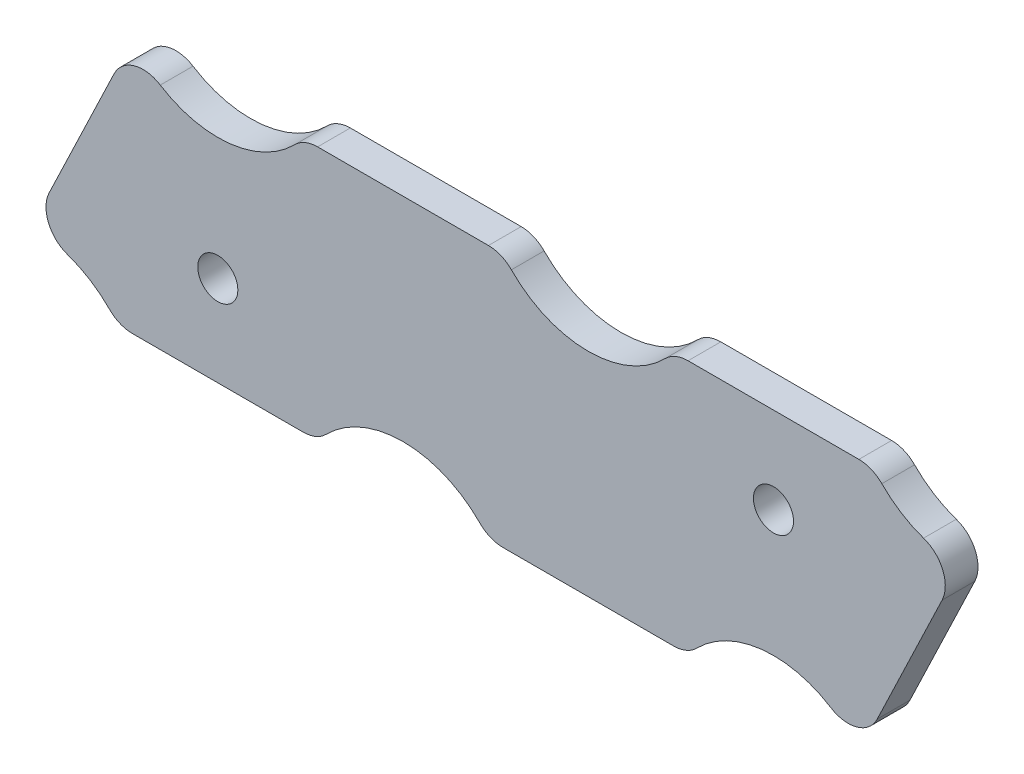
SolidWorks part; units mm, degrees
material "3003-H14"
ref_plane "X-Y Datum" through (0, 0, 0) normal (0, 0, 1) x (1, 0, 0)
ref_plane "X-Z Datum" through (0, 0, 0) normal (0, 1, 0) x (1, 0, 0)
ref_plane "Y-Z Datum" through (0, 0, 0) normal (1, 0, 0) x (0, 0, -1)
sketch "Sketch3" plane through (0, 0, 0) normal (0, 0, 1) x (1, 0, 0)
  line L0 (10.775, 10.775) -> (22.275, 34.775) construction
  line L1 (0, 0) -> (156.4633, 0) construction
  line L2 (0, 0) -> (0, 56.3098) construction
  line L3 (0, 56.3098) -> (156.4633, 56.3098) construction
  line L4 (156.4633, 0) -> (156.4633, 56.3098) construction
  line L5 (33.775, 10.775) -> (45.275, 34.775) construction
  line L6 (56.775, 10.775) -> (68.275, 34.775) construction
  line L7 (16.525, 22.775) -> (62.525, 22.775) construction
  line L8 (33.775, 10.775) -> (22.275, 34.775) construction
  line L9 (45.275, 34.775) -> (56.775, 10.775) construction
  line L10 (10.775, 10.775) -> (33.775, 10.775) construction
  line L11 (56.775, 10.775) -> (33.775, 10.775) construction
  line L12 (22.275, 34.775) -> (45.275, 34.775) construction
  line L13 (68.275, 34.775) -> (45.275, 34.775) construction
  line L14 (22.275, 34.775) -> (22.275, 10.775) construction
  line L15 (45.275, 10.775) -> (45.275, 34.775) construction
  line L16 (33.775, 10.775) -> (33.775, 34.775) construction
  line L17 (56.775, 34.775) -> (56.775, 10.775) construction
  line L18 (13.4804, 9.4786) -> (24.9804, 33.4786)
  line L19 (36.4804, 9.4786) -> (47.9804, 33.4786)
  line L20 (59.4804, 9.4786) -> (70.9804, 33.4786)
  line L21 (8.0696, 12.0714) -> (19.5696, 36.0714)
  line L22 (31.0696, 12.0714) -> (42.5696, 36.0714)
  line L23 (54.0696, 12.0714) -> (65.5696, 36.0714)
  line L24 (17.8152, 18.525) -> (57.1619, 18.525)
  line L25 (21.8881, 27.025) -> (61.2348, 27.025)
  line L26 (16.525, 27.025) -> (62.525, 27.025) construction
  line L27 (16.525, 18.525) -> (62.525, 18.525) construction
  line L28 (16.0692, 14.8813) -> (28.4808, 14.8813)
  line L29 (39.9808, 30.6687) -> (27.5692, 30.6687)
  line L48 (56.775, 10.775) -> (68.275, 10.775) construction
  line L49 (68.275, 10.775) -> (68.275, 34.775) construction
  line L50 (62.9808, 30.6687) -> (50.5692, 30.6687)
  line L51 (39.0692, 14.8813) -> (51.4808, 14.8813)
  circle A0 centre (10.775, 10.775) radius 10.775 construction
  circle A1 centre (33.775, 10.775) radius 10.775 construction
  circle A2 centre (22.275, 34.775) radius 10.775 construction
  circle A3 centre (45.275, 34.775) radius 10.775 construction
  circle A4 centre (68.275, 34.775) radius 10.775 construction
  circle A5 centre (56.775, 10.775) radius 10.775 construction
  circle A6 centre (10.775, 10.775) radius 4.7 construction
  circle A7 centre (33.775, 10.775) radius 4.7 construction
  circle A8 centre (56.775, 10.775) radius 4.7 construction
  circle A9 centre (68.275, 34.775) radius 4.7 construction
  circle A10 centre (45.275, 34.775) radius 4.7 construction
  circle A11 centre (22.275, 34.775) radius 4.7 construction
  circle A12 centre (22.275, 34.775) radius 6.7
  circle A13 centre (10.775, 10.775) radius 6.7
  circle A14 centre (33.775, 10.775) radius 6.7
  circle A15 centre (45.275, 34.775) radius 6.7
  circle A16 centre (68.275, 34.775) radius 6.7
  circle A17 centre (56.775, 10.775) radius 6.7
  circle A18 centre (125.775, 10.775) radius 10.775 construction
  circle A19 centre (102.775, 10.775) radius 10.775 construction
  circle A20 centre (79.775, 10.775) radius 10.775 construction
  circle A21 centre (91.275, 34.775) radius 10.775 construction
  circle A22 centre (114.275, 34.775) radius 10.775 construction
  circle A23 centre (137.275, 34.775) radius 10.775 construction
  dimension "D1" = 21.55
  dimension "D9" = 9.4
  dimension "D2" = 23
  dimension "D3" = 24
  dimension "D4" = 11.5
  dimension "D6" = 23
  dimension "D8" = 23
  dimension "D10" = 3
  dimension "D11" = 3
  dimension "D12" = 4.25
  dimension "D13" = 4.25
  dimension "D14" = 2
  dimension "D5" = 6
  dimension "D7" = 5
extrude "Boss-Extrude1" add sketch "Sketch3" along normal blind 2.032 contours L17 | L17 | L17 | L17 | L49 | A13 L18 A12 L21 | L25 L18 L24 L22 | L25 L22 L24 L19 | L25 L19 L24 L23 | A17 L20 A16 L23 | A14 L19 L24 L22 | A15 L22 L25 L19 | A14 L22 L24 L18 L28 | A12 L18 L25 L22 L29 | A17 L23 L24 L19 L51 | A15 L19 L25 L23 L50 region at (16.525, 22.775, 0) region at (24.1977, 16.8116, 0) region at (28.025, 22.775, 0) region at (31.8523, 28.7384, 0) region at (37.7051, 17.4114, 0) region at (39.525, 22.775, 0) region at (41.3449, 28.1386, 0) region at (47.1977, 16.8116, 0) region at (51.025, 22.775, 0) region at (54.8523, 28.7384, 0) region at (62.525, 22.775, 0)
ref_plane "Plane1" through (68.275, 0, 0) normal (1, 0, 0) x (0, 0, -1)
fillet "Fillet1" radius 2 12 edges at (62.9808, 30.6687, 1.016) (50.5692, 30.6687, 1.016) (39.9808, 30.6687, 1.016) (27.5692, 30.6687, 1.016) (16.0692, 14.8813, 1.016) (28.4808, 14.8813, 1.016) (39.0692, 14.8813, 1.016) (51.4808, 14.8813, 1.016) (68.3917, 28.076, 1.016) (62.0692, 14.8813, 1.016) (10.6583, 17.474, 1.016) (16.9808, 30.6687, 1.016)
sketch "Sketch4" plane through (0, 0, 2.032) normal (0, 0, 1) x (1, 0, 0)
  circle A0 centre (22.275, 20.4921) radius 1.2446
  circle A1 centre (56.775, 25.307) radius 1.2446
  point P0 (56.775, 25.307)
  point P1 (22.275, 20.4921)
  dimension "D1" = 2.4892
extrude "Cut-Extrude1" cut sketch "Sketch4" against normal through all
sketch "Sketch5" [suppressed] plane through (0, 0, 2.032) normal (0, 0, 1) x (1, 0, 0)
  line L0 (13.8196, 24.0714) -> (66.4728, 24.0714)
  line L1 (11.8041, 19.8652) -> (15.835, 28.2776) construction
  line L2 (63.215, 17.2724) -> (67.2459, 25.6848) construction
  line L3 (65.2304, 21.4786) -> (12.5772, 21.4786)
  line L5 (40.1462, 24.0714) -> (40.1462, 21.4786)
  line L6 (38.9038, 21.4786) -> (38.9038, 24.0714)
  line L7 (38.9038, 22.775) -> (40.1462, 22.775)
  line L9 (16.025, 27.275) -> (63.025, 27.275)
  line L10 (16.025, 27.275) -> (16.025, 18.275)
  line L11 (16.025, 18.275) -> (63.025, 18.275)
  line L12 (63.025, 27.275) -> (63.025, 18.275)
  line L13 (16.025, 27.275) -> (63.025, 18.275) construction
  line L14 (16.025, 18.275) -> (63.025, 27.275) construction
  point P11 (40.1462, 24.0714)
  point P15 (39.525, 22.775)
  dimension "D1" = 47
  dimension "D2" = 9
